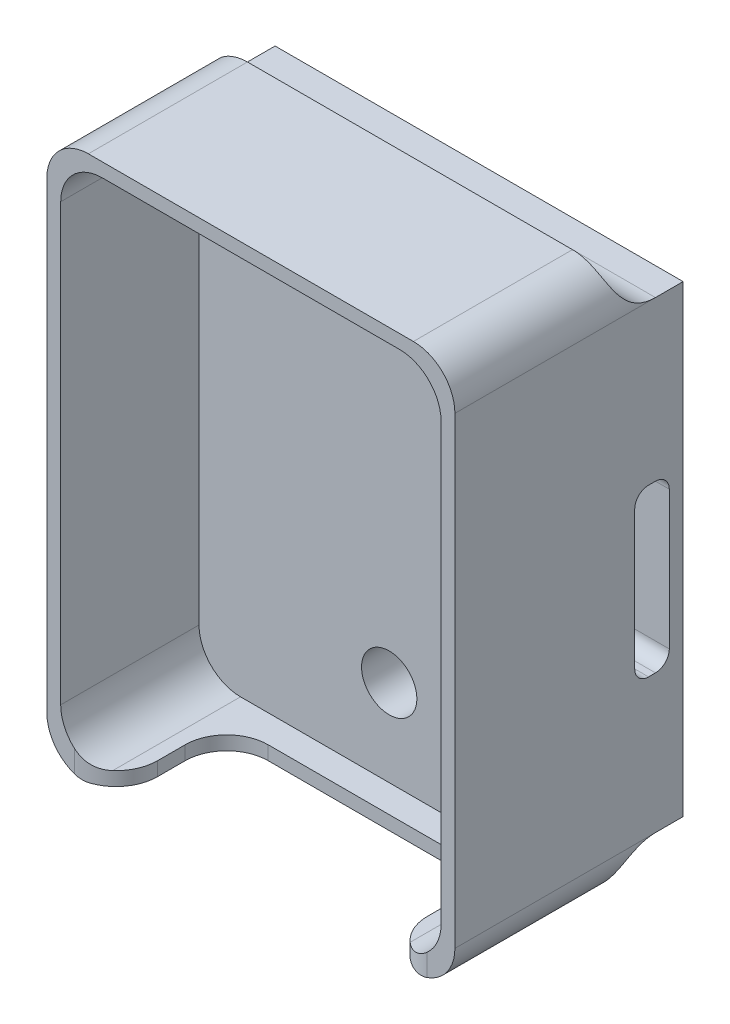
SolidWorks part; units mm, degrees
material "ABS"
ref_plane "Front Plane" through (0, 0, 0) normal (0, 0, 1) x (1, 0, 0)
ref_plane "Top Plane" through (0, 0, 0) normal (0, 1, 0) x (1, 0, 0)
ref_plane "Right Plane" through (0, 0, 0) normal (1, 0, 0) x (0, 0, -1)
sketch "Sketch1" plane through (0, 0, 0) normal (0, 0, 1) x (1, 0, 0)
  line L1 (-34.925, 47.625) -> (34.925, 47.625)
  line L2 (-34.925, 47.625) -> (-34.925, -47.625)
  line L3 (-34.925, -47.625) -> (34.925, -47.625)
  line L4 (34.925, 47.625) -> (34.925, -47.625)
  line L5 (-34.925, 47.625) -> (34.925, -47.625) construction
  line L6 (-34.925, -47.625) -> (34.925, 47.625) construction
  line L7 (-37.465, 50.165) -> (37.465, 50.165)
  line L8 (-37.465, 50.165) -> (-37.465, -50.165)
  line L9 (-37.465, -50.165) -> (37.465, -50.165)
  line L10 (37.465, 50.165) -> (37.465, -50.165)
  line L11 (-37.465, 50.165) -> (37.465, -50.165) construction
  line L12 (-37.465, -50.165) -> (37.465, 50.165) construction
  point P0 (0, 0)
  point P6 (0, 0)
  dimension "D1" = 95.25
  dimension "D2" = 69.85
  dimension "D3" = 2.54
  dimension "D4" = 2.54
extrude "Boss-Extrude1" add sketch "Sketch1" along normal blind 25.4
sketch "Sketch2" plane through (0, 0, 0) normal (0, 0, -1) x (-1, 0, 0)
  line L1 (-37.465, 50.165) -> (37.465, 50.165)
  line L2 (-37.465, 50.165) -> (-37.465, -50.165)
  line L3 (-37.465, -50.165) -> (37.465, -50.165)
  line L4 (37.465, 50.165) -> (37.465, -50.165)
extrude "Boss-Extrude2" add sketch "Sketch2" along normal blind 3.81
fillet "Fillet1" radius 7.62 4 edges at (34.925, -47.625, 12.7) (-34.925, -47.625, 12.7) (-34.925, 47.625, 12.7) (34.925, 47.625, 12.7)
sketch "Sketch3" plane through (0, -50.165, 0) normal (0, -1, 0) x (-1, 0, 0)
  line L0 (37.465, -25.4) -> (-37.465, -25.4) construction
  line L1 (24.765, -25.4) -> (-24.765, -25.4)
  line L2 (24.765, -25.4) -> (24.765, -5.08)
  line L3 (24.765, -5.08) -> (-24.765, -5.08)
  line L4 (-24.765, -25.4) -> (-24.765, -5.08)
  line L5 (37.465, -25.4) -> (37.465, 3.81) construction
  line L6 (-37.465, -25.4) -> (-37.465, 3.81) construction
  dimension "D1" = 12.7
  dimension "D2" = 12.7
  dimension "D3" = 20.32
extrude "Cut-Extrude1" cut sketch "Sketch3" against normal blind 11.43
fillet "Fillet2" radius 7.62 4 edges at (24.765, -48.895, 25.4) (-24.765, -48.895, 25.4) (-24.765, -48.895, 5.08) (24.765, -48.895, 5.08)
fillet "Fillet3" radius 7.62 4 edges at (37.465, 50.165, 10.795) (37.465, -50.165, 10.795) (-37.465, -50.165, 10.795) (-37.465, 50.165, 10.795)
sketch "Sketch4" plane through (37.465, 0, 0) normal (1, 0, 0) x (0, 0, -1)
  line L1 (3.81, 42.545) -> (16.51, 42.545)
  line L2 (3.81, 42.545) -> (3.81, -42.545)
  line L3 (3.81, -42.545) -> (16.51, -42.545)
  line L4 (16.51, 42.545) -> (16.51, -42.545)
  dimension "D1" = 12.7
extrude "Boss-Extrude3" add sketch "Sketch4" against normal up to surface (74.93 mm away) up to face at (-37.465, 0, 10.795)
fillet "Fillet4" radius 7.62 2 edges at (0, -42.545, -3.81) (0, 42.545, -3.81)
sketch "Sketch5" plane through (37.465, 0, 0) normal (1, 0, 0) x (0, 0, -1)
  line L0 (16.51, -42.545) -> (16.51, 42.545) construction
  line L1 (10.16, 13.335) -> (11.43, 13.335)
  line L2 (7.62, 10.795) -> (7.62, -14.605)
  line L3 (10.16, -17.145) -> (11.43, -17.145)
  line L4 (13.97, 10.795) -> (13.97, -14.605)
  line L5 (11.43, -42.545) -> (16.51, -42.545) construction
  arc A0 (11.43, -17.145) -> (13.97, -14.605) centre (11.43, -14.605) ccw
  arc A1 (7.62, -14.605) -> (10.16, -17.145) centre (10.16, -14.605) ccw
  arc A2 (11.43, 13.335) -> (13.97, 10.795) centre (11.43, 10.795) cw
  arc A3 (10.16, 13.335) -> (7.62, 10.795) centre (10.16, 10.795) ccw
  point P10 (13.97, -17.145)
  point P13 (7.62, -17.145)
  point P16 (13.97, 13.335)
  dimension "D5" = 2.54
  dimension "D1" = 30.48
  dimension "D2" = 2.54
  dimension "D3" = 6.35
  dimension "D4" = 25.4
extrude "Cut-Extrude2" cut sketch "Sketch5" against normal through all
sketch "Sketch6" plane through (0, 0, 0) normal (0, 0, 1) x (1, 0, 0)
  circle A0 centre (0, 31.75) radius 2.54
  circle A1 centre (0, -31.75) radius 2.54
  dimension "D1" = 5.08
  dimension "D2" = 5.08
  dimension "D3" = 31.75
  dimension "D4" = 31.75
extrude "Cut-Extrude3" cut sketch "Sketch6" against normal through all
sketch "Sketch7" plane through (0, 0, 0) normal (0, 0, 1) x (1, 0, 0)
  circle A0 centre (0, 31.75) radius 5.08
  circle A1 centre (0, -31.75) radius 5.08
  dimension "D1" = 10.16
  dimension "D2" = 10.16
extrude "Cut-Extrude4" cut sketch "Sketch7" against normal blind 8.89
